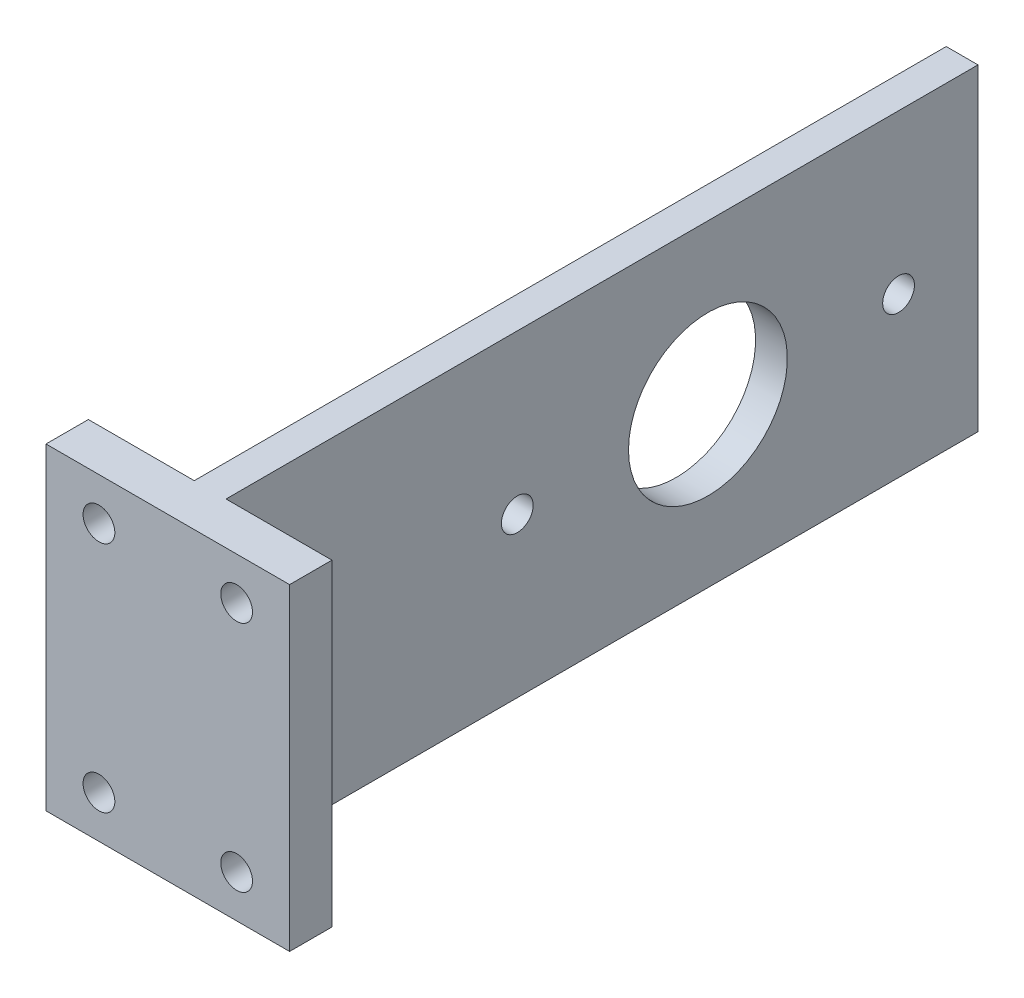
SolidWorks part; units mm, degrees
ref_plane "Front Plane" through (0, 0, 0) normal (0, 0, 1) x (1, 0, 0)
ref_plane "Top Plane" through (0, 0, 0) normal (0, 1, 0) x (1, 0, 0)
ref_plane "Right Plane" through (0, 0, 0) normal (1, 0, 0) x (0, 0, -1)
sketch "Sketch1" plane through (0, 0, 0) normal (0, 1, 0) x (1, 0, 0)
  line L0 (0, 35.1176) -> (0, -36.8824) construction
  line L1 (-40.3529, 0) -> (41.8824, 0) construction
  line L2 (-11.5, 4) -> (-1.5, 4)
  line L3 (-1.5, 4) -> (-1.5, 75)
  line L4 (-1.5, 75) -> (1.5, 75)
  line L5 (-11.5, 4) -> (-11.5, 0)
  line L6 (-11.5, 0) -> (11.5, 0)
  line L7 (11.5, 4) -> (11.5, 0)
  line L8 (1.5, 4) -> (1.5, 75)
  line L9 (11.5, 4) -> (1.5, 4)
  point P12 (0, 0)
  point P14 (0, 75)
  dimension "D1" = 4
  dimension "D2" = 1.5
  dimension "D3" = 71
  dimension "D4" = 10
extrude "Boss-Extrude1" add sketch "Sketch1" along normal blind 30
sketch "Sketch2" plane through (-1.5, 0, 0) normal (-1, 0, 0) x (0, 0, 1)
  line L0 (-75, 30) -> (-4, 30) construction
  line L3 (-75, 30) -> (-75, 0) construction
  circle A0 centre (-67.5, 15) radius 1.5
  circle A1 centre (-31.5, 15) radius 1.5
  circle A2 centre (-49.5, 15) radius 7.5
  dimension "D1" = 15
  dimension "D2" = 3
  dimension "D3" = 15
  dimension "D4" = 36
  dimension "D5" = 7.5
  dimension "D6" = 18
extrude "Cut-Extrude1" cut sketch "Sketch2" against normal through all
sketch "Sketch3" plane through (0, 0, 0) normal (0, 0, 1) x (1, 0, 0)
  line L0 (0, 30.8618) -> (0, -1.0393) construction
  line L1 (-21.25, 15) -> (21.7222, 15) construction
  line L2 (-11.5, 30) -> (11.5, 30) construction
  line L3 (-11.5, 30) -> (-11.5, 0) construction
  line L4 (11.5, 30) -> (11.5, 0) construction
  line L5 (-11.5, 0) -> (11.5, 0) construction
  circle A0 centre (-6.5, 26) radius 1.5
  circle A1 centre (-6.5, 4) radius 1.5
  circle A2 centre (6.5, 4) radius 1.5
  circle A3 centre (6.5, 26) radius 1.5
  dimension "D2" = 3
  dimension "D3" = 4
  dimension "D4" = 5
  dimension "D5" = 5
  dimension "D6" = 4
  dimension "D1" = 15
extrude "Cut-Extrude2" cut sketch "Sketch3" against normal through all
